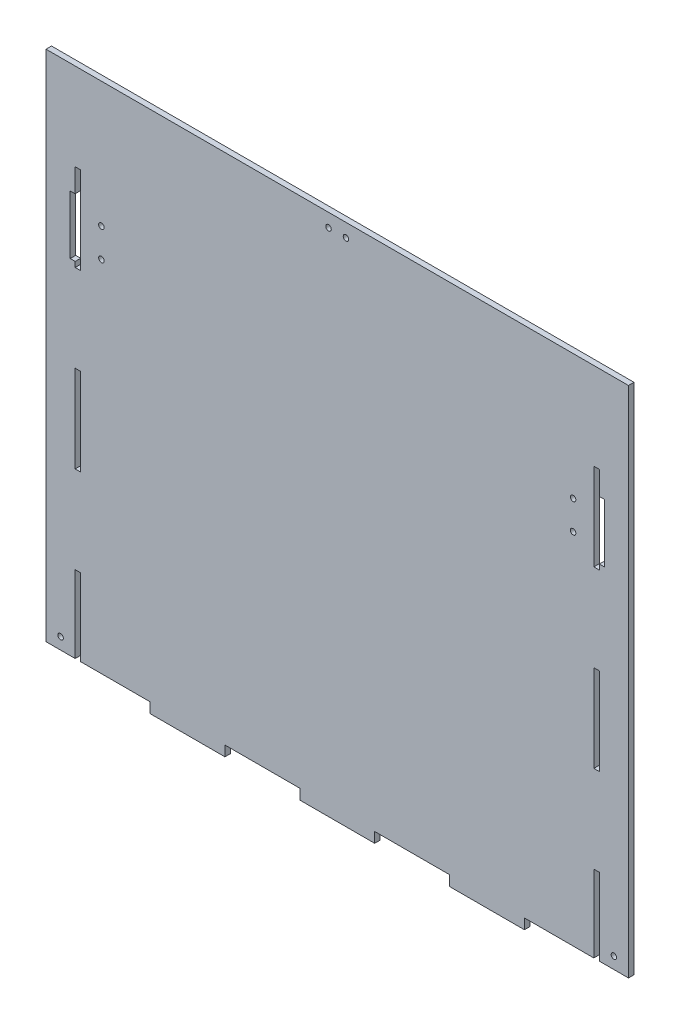
SolidWorks part; units mm, degrees
ref_plane "Front Plane" through (0, 0, 0) normal (0, 0, 1) x (1, 0, 0)
ref_plane "Top Plane" through (0, 0, 0) normal (0, 1, 0) x (1, 0, 0)
ref_plane "Right Plane" through (0, 0, 0) normal (1, 0, 0) x (0, 0, -1)
sketch "Sketch1" plane through (0, 0, 0) normal (0, 0, 1) x (1, 0, 0)
  line L1 (0, 139.7) -> (0, -139.7) construction
  line L2 (-139.7, 139.7) -> (139.7, 139.7)
  line L3 (-139.7, 139.7) -> (-139.7, -139.7)
  line L4 (-139.7, -139.7) -> (139.7, -139.7)
  line L5 (139.7, 139.7) -> (139.7, -139.7)
  line L6 (-139.7, 0) -> (139.7, 0) construction
  line L7 (-139.7, 92.202) -> (-139.7, 44.704)
  line L8 (-139.7, 139.7) -> (-142.6972, 139.7)
  line L96 (-139.7, 139.7) -> (-139.7, 92.202)
  line L97 (-139.7, 92.202) -> (-142.6972, 92.202)
  line L98 (-142.6972, 139.7) -> (-142.6972, 92.202)
  line L99 (139.7, 139.7) -> (142.6972, 139.7)
  line L100 (139.7, 139.7) -> (139.7, 92.202)
  line L101 (139.7, 92.202) -> (142.6972, 92.202)
  line L102 (142.6972, 139.7) -> (142.6972, 92.202)
  line L103 (-101.9266, -139.7) -> (-142.6972, -139.7)
  line L104 (-101.9266, -139.7) -> (-101.9266, -145.288)
  line L105 (-101.9266, -145.288) -> (-142.6972, -145.288)
  line L106 (-142.6972, -139.7) -> (-142.6972, -145.288)
  line L107 (-139.7, 92.202) -> (-142.6972, 92.202)
  line L108 (-142.6972, 92.202) -> (-142.6972, 44.704)
  line L109 (-139.7, 44.704) -> (-142.6972, 44.704)
  line L110 (139.7, 92.202) -> (139.7, 44.704)
  line L111 (139.7, 92.202) -> (142.6972, 92.202)
  line L112 (142.6972, 92.202) -> (142.6972, 44.704)
  line L113 (139.7, 44.704) -> (142.6972, 44.704)
  line L114 (-139.7, 44.704) -> (-139.7, -2.794)
  line L115 (-139.7, 44.704) -> (-142.6972, 44.704)
  line L116 (-142.6972, 44.704) -> (-142.6972, -2.794)
  line L117 (-139.7, -2.794) -> (-142.6972, -2.794)
  line L118 (139.7, 44.704) -> (139.7, -2.794)
  line L119 (139.7, 44.704) -> (142.6972, 44.704)
  line L120 (142.6972, 44.704) -> (142.6972, -2.794)
  line L121 (139.7, -2.794) -> (142.6972, -2.794)
  line L122 (-139.7, -2.794) -> (-139.7, -50.292)
  line L123 (-139.7, -2.794) -> (-142.6972, -2.794)
  line L124 (-142.6972, -2.794) -> (-142.6972, -50.292)
  line L125 (-139.7, -50.292) -> (-142.6972, -50.292)
  line L126 (139.7, -2.794) -> (139.7, -50.292)
  line L127 (139.7, -2.794) -> (142.6972, -2.794)
  line L128 (142.6972, -2.794) -> (142.6972, -50.292)
  line L129 (139.7, -50.292) -> (142.6972, -50.292)
  line L130 (-139.7, -50.292) -> (-139.7, -97.79)
  line L131 (-139.7, -50.292) -> (-142.6972, -50.292)
  line L132 (-142.6972, -50.292) -> (-142.6972, -97.79)
  line L133 (-139.7, -97.79) -> (-142.6972, -97.79)
  line L134 (139.7, -50.292) -> (139.7, -97.79)
  line L135 (139.7, -50.292) -> (142.6972, -50.292)
  line L136 (142.6972, -50.292) -> (142.6972, -97.79)
  line L137 (139.7, -97.79) -> (142.6972, -97.79)
  line L138 (-139.7, -97.79) -> (-139.7, -145.288)
  line L139 (-139.7, -97.79) -> (-142.6972, -97.79)
  line L140 (-142.6972, -97.79) -> (-142.6972, -145.288)
  line L141 (-139.7, -145.288) -> (-142.6972, -145.288)
  line L142 (139.7, -97.79) -> (139.7, -145.288)
  line L143 (139.7, -97.79) -> (142.6972, -97.79)
  line L144 (142.6972, -97.79) -> (142.6972, -145.288)
  line L145 (139.7, -145.288) -> (142.6972, -145.288)
  line L146 (-61.1559, -139.7) -> (-61.1559, -145.288)
  line L147 (-61.1559, -139.7) -> (-101.9266, -139.7)
  line L148 (-101.9266, -139.7) -> (-101.9266, -145.288)
  line L149 (-61.1559, -145.288) -> (-101.9266, -145.288)
  line L150 (-20.3853, -139.7) -> (-20.3853, -145.288)
  line L151 (-20.3853, -139.7) -> (-61.1559, -139.7)
  line L152 (-61.1559, -139.7) -> (-61.1559, -145.288)
  line L153 (-20.3853, -145.288) -> (-61.1559, -145.288)
  line L154 (20.3853, -139.7) -> (20.3853, -145.288)
  line L155 (20.3853, -139.7) -> (-20.3853, -139.7)
  line L156 (-20.3853, -139.7) -> (-20.3853, -145.288)
  line L157 (20.3853, -145.288) -> (-20.3853, -145.288)
  line L158 (61.1559, -139.7) -> (61.1559, -145.288)
  line L159 (61.1559, -139.7) -> (20.3853, -139.7)
  line L160 (20.3853, -139.7) -> (20.3853, -145.288)
  line L161 (61.1559, -145.288) -> (20.3853, -145.288)
  line L162 (101.9266, -139.7) -> (101.9266, -145.288)
  line L163 (101.9266, -139.7) -> (61.1559, -139.7)
  line L164 (61.1559, -139.7) -> (61.1559, -145.288)
  line L165 (101.9266, -145.288) -> (61.1559, -145.288)
  line L166 (142.6972, -139.7) -> (142.6972, -145.288)
  line L167 (142.6972, -139.7) -> (101.9266, -139.7)
  line L168 (101.9266, -139.7) -> (101.9266, -145.288)
  line L169 (142.6972, -145.288) -> (101.9266, -145.288)
  point P8 (0, 0)
  dimension "D1" = 279.4
  dimension "D2" = 279.4
  dimension "D3" = 285.3944
  dimension "D4" = 284.988
  dimension "D6" = 47.498
  dimension "D8" = 40.7706
  dimension "D5" = 6
  dimension "D7" = 7
extrude "Boss-Extrude1" add sketch "Sketch1" along normal mid plane 2.9972 contours L5 L2 L3 L4 | L133 L3 L125 L132 | L149 L146 L4 L104 | L157 L154 L4 L150 | L165 L162 L4 L158 | L5 L137 L136 L129 | L5 L121 L120 L113 | L102 L99 L5 L101 | L117 L3 L109 L116 | L8 L98 L97 L3 region at (0, 0, 0) region at (-141.1986, 115.951, 0) region at (141.1986, 115.951, 0) region at (-141.1986, 20.955, 0) region at (141.1986, 20.955, 0) region at (-141.1986, -74.041, 0) region at (141.1986, -74.041, 0) region at (-81.5413, -142.494, 0) region at (81.5413, -142.494, 0) region at (0, -142.494, 0)
sketch "Sketch2" plane through (0, 0, 1.4986) normal (0, 0, 1) x (1, 0, 0)
  line L0 (38.1, 114.3) -> (-38.1, 114.3) construction
  line L1 (38.1, 101.6) -> (-38.1, 101.6)
  line L2 (38.1, 127) -> (-38.1, 127)
  line L3 (-142.6972, 139.7) -> (142.6972, 139.7) construction
  arc A0 (38.1, 101.6) -> (38.1, 127) centre (38.1, 114.3) ccw
  arc A1 (-38.1, 127) -> (-38.1, 101.6) centre (-38.1, 114.3) ccw
  point P2 (0, 114.3)
  dimension "D1" = 25.4
  dimension "D2" = 76.2
  dimension "D3" = 12.7
extrude "Cut-Extrude1" [suppressed] cut sketch "Sketch2" against normal through all
sketch "Sketch3" plane through (0, 0, 1.4986) normal (0, 0, 1) x (1, 0, 0)
  line L0 (-128.4097, 71.374) -> (-128.4097, 55.626) construction
  line L1 (128.4097, 71.374) -> (128.4097, 55.626) construction
  line L2 (-128.4097, 63.5) -> (128.4097, 63.5) construction
  line L3 (0, 0) -> (0, 63.5) construction
  line L4 (-142.6972, 139.7) -> (-142.6972, 92.202) construction
  line L5 (-142.6972, 139.7) -> (142.6972, 139.7) construction
  circle A0 centre (-128.4097, 71.374) radius 1.5
  circle A1 centre (-128.4097, 55.626) radius 1.5
  circle A2 centre (128.4097, 71.374) radius 1.5
  circle A3 centre (128.4097, 55.626) radius 1.5
  dimension "D1" = 3
  dimension "D2" = 15.748
  dimension "D3" = 14.2875
  dimension "D4" = 76.2
extrude "Cut-Extrude2" cut sketch "Sketch3" against normal through all
sketch "Sketch4" plane through (0, 0, 1.4986) normal (0, 0, 1) x (1, 0, 0)
  line L0 (101.9266, -139.7) -> (139.7, -139.7) construction
  line L1 (-142.6972, 139.7) -> (-158.5722, 139.7)
  line L2 (-142.6972, 139.7) -> (-142.6972, -139.7)
  line L3 (-142.6972, -139.7) -> (-158.5722, -139.7)
  line L4 (-158.5722, 139.7) -> (-158.5722, -139.7)
  line L5 (142.6972, 139.7) -> (158.5722, 139.7)
  line L6 (142.6972, 139.7) -> (142.6972, -139.7)
  line L7 (142.6972, -139.7) -> (158.5722, -139.7)
  line L8 (158.5722, 139.7) -> (158.5722, -139.7)
  line L9 (145.3972, 63.5) -> (128.4097, 63.5) construction
  line L10 (-142.6972, 79.4385) -> (-145.3972, 79.4385)
  line L11 (-142.6972, 79.4385) -> (-142.6972, 47.5615)
  line L12 (-142.6972, 47.5615) -> (-145.3972, 47.5615)
  line L13 (-145.3972, 79.4385) -> (-145.3972, 47.5615)
  line L14 (142.6972, 79.4385) -> (145.3972, 79.4385)
  line L15 (142.6972, 79.4385) -> (142.6972, 47.5615)
  line L16 (142.6972, 47.5615) -> (145.3972, 47.5615)
  line L17 (145.3972, 79.4385) -> (145.3972, 47.5615)
  line L18 (128.4097, 55.626) -> (128.4097, 71.374) construction
  line L19 (-150.6347, -133.35) -> (-150.6347, -139.7) construction
  line L20 (-139.7, -139.7) -> (-101.9266, -139.7) construction
  line L21 (150.6347, -133.35) -> (-150.6347, -133.35) construction
  line L22 (0, -133.35) -> (0, 0) construction
  circle A0 centre (-150.6347, -133.35) radius 1.5
  circle A1 centre (150.6347, -133.35) radius 1.5
  point P27 (128.4097, 63.5)
  line M15 (142.6972, 92.202) -> (142.6972, 139.7)
  line M17 (-142.6972, 139.7) -> (-142.6972, 92.202)
  line M21 (-142.6972, 44.704) -> (-142.6972, -2.794)
  line M25 (-142.6972, -50.292) -> (-142.6972, -97.79)
  line M43 (142.6972, -97.79) -> (142.6972, -50.292)
  line M47 (142.6972, -2.794) -> (142.6972, 44.704)
  dimension "D6" = 3
  dimension "D1" = 15.875
  dimension "D2" = 31.877
  dimension "D3" = 2.7
  dimension "D5" = 6.35
extrude "Boss-Extrude2" add sketch "Sketch4" against normal up to surface (2.9972 mm away) contours L13 L10 L2 L1 L4 L3 L12 M17 M25 M21 | L14 L17 L16 L6 L7 L8 L5 M47 M43 M15 region at (-150.7653, -1.0415, 1.4986) region at (150.7653, -1.0415, 1.4986) up to face at (-126.9097, 55.626, -1.4986)
sketch "Sketch5" plane through (0, 0, 1.4986) normal (0, 0, 1) x (1, 0, 0)
  line L0 (-4.7625, 132.3975) -> (4.7625, 132.3975) construction
  line L1 (0, 132.3975) -> (0, 139.7) construction
  line L2 (-158.5722, 139.7) -> (158.5722, 139.7) construction
  circle A0 centre (-4.7625, 132.3975) radius 1.5
  circle A1 centre (4.7625, 132.3975) radius 1.5
  dimension "D1" = 3
  dimension "D2" = 9.525
  dimension "D3" = 7.3025
extrude "Cut-Extrude3" cut sketch "Sketch5" against normal through all
equation "\"wallthickness\"= .118in"
equation "\"floorThickness\"= .220in"
equation "\"D3@Sketch1\"=\"wallthickness\"*2+\"D1@Sketch1\""
equation "\"D4@Sketch1\"=\"floorThickness\"+\"D2@Sketch1\""
equation "\"D6@Sketch1\"=\"D4@Sketch1\"/\"D5@Sketch1\""
equation "\"D8@Sketch1\"=\"D3@Sketch1\"/\"D7@Sketch1\""
equation "\"D1@Boss-Extrude1\"=\"wallthickness\""
